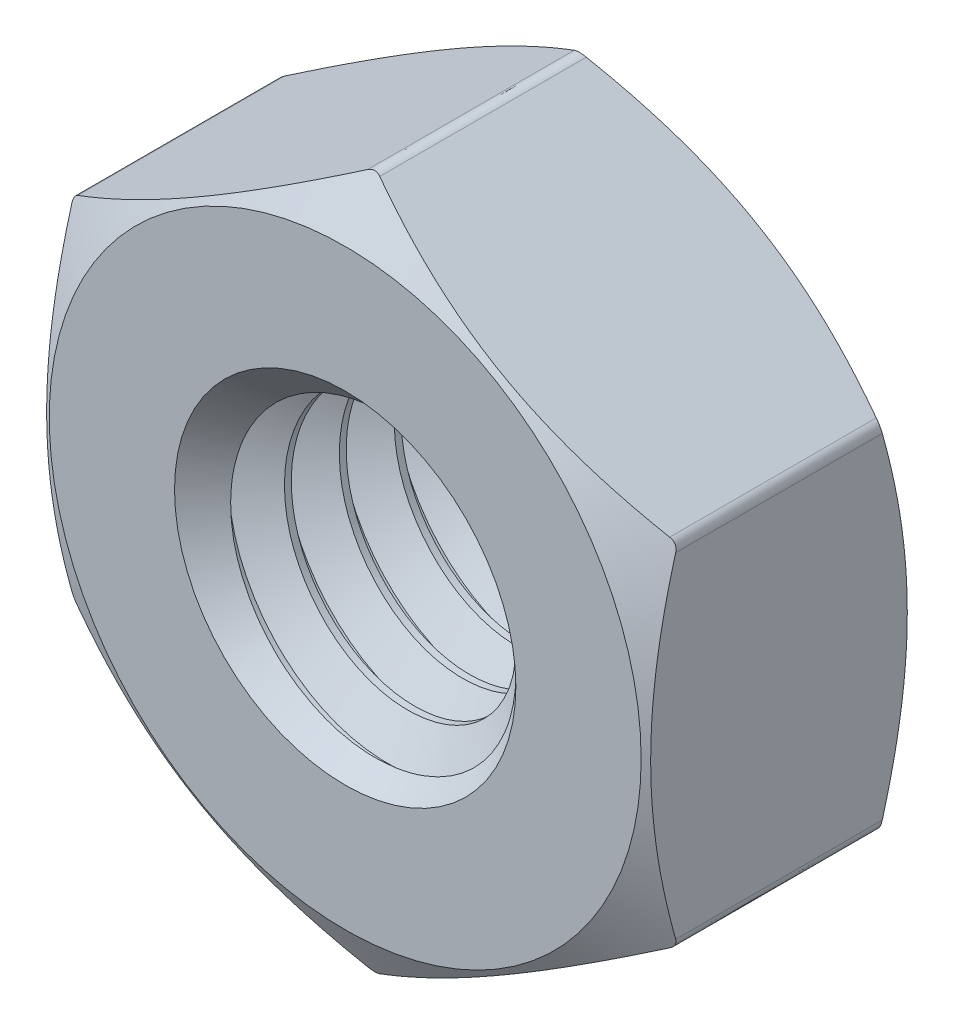
SolidWorks part; units mm, degrees
material "AISI 316 Annealed Stainless Steel Bar (SS)"
ref_plane "Front Plane" through (0, 0, 0) normal (0, 0, 1) x (1, 0, 0)
ref_plane "Top Plane" through (0, 0, 0) normal (0, 1, 0) x (1, 0, 0)
ref_plane "Right Plane" through (0, 0, 0) normal (1, 0, 0) x (0, 0, -1)
sketch "Sketch1" plane through (0, 0, 0) normal (0, 0, 1) x (1, 0, 0)
  line L0 (0, -3.1754) -> (0, 3.1754) construction
  line L1 (0, -3.1754) -> (2.75, -1.5877) construction
  line L2 (2.75, -1.5877) -> (2.75, 1.5877) construction
  line L3 (2.75, 1.5877) -> (0, 3.1754) construction
  line L4 (0, 3.1754) -> (-2.75, 1.5877) construction
  line L5 (-2.75, 1.5877) -> (-2.75, -1.5877) construction
  line L6 (-2.75, -1.5877) -> (0, -3.1754) construction
  line L7 (-2.75, 0) -> (2.75, 0) construction
  line L8 (0, 0) -> (0.75, -1.299) construction
  circle A0 centre (0, 0) radius 2.75 construction
  circle A1 centre (0, 0) radius 1.5 construction
  point P11 (0, 0)
  point P12 (0, -1.5)
  point P14 (1.5, 0)
  point P15 (0, 1.5)
  point P16 (-1.5, 0)
  point P19 (0.75, -1.299)
  dimension "Thread Diameter" = 3
  dimension "Width" = 5.5
  dimension "D1" = 30
sketch "Sketch2" plane through (0, 0, 0) normal (1, 0, 0) x (0, 0, -1)
  line L0 (0, -2.75) -> (0, 2.75) construction
  line L1 (-1.2, 2.75) -> (1.2, 2.75) construction
  line L2 (-1.2, 2.75) -> (-1.2, -2.75) construction
  line L3 (-1.2, -2.75) -> (1.2, -2.75) construction
  line L4 (1.2, 2.75) -> (1.2, -2.75) construction
  line L5 (1.2, 0) -> (-1.2, 0) construction
  line L8 (-1.2, 1.5) -> (1.2, 1.5) construction
  line L9 (-1.2, -1.5) -> (1.2, -1.5) construction
  line L10 (-1.6688, 1.5541) -> (-1.1687, 1.5541) construction
  line L11 (-1.1687, 1.5541) -> (-1.4187, 1.1211) construction
  line L12 (-1.4187, 1.1211) -> (-1.6688, 1.5541) construction
  line L13 (-1.6531, 1.5271) -> (-1.1844, 1.5271) construction
  line L14 (-1.6375, 1.5) -> (-1.2, 1.5) construction
  line L15 (-1.45, 1.1752) -> (-1.3875, 1.1752) construction
  line L16 (-1.4187, 1.1752) -> (-1.4187, 1.1211) construction
  line L17 (-1.4187, 1.5541) -> (-1.4187, 1.5) construction
  point P8 (0, 0)
  point P29 (-1.4187, 1.5271)
  dimension "Height" = 2.4
  dimension "Thread Pitch" = 0.5
  dimension "D2" = 0.0625
sketch "Sketch3" plane through (0, 0, 0) normal (0, 0, 1) x (1, 0, 0)
  line L1 (0, -3.1754) -> (2.75, -1.5877)
  line L2 (2.75, -1.5877) -> (2.75, 1.5877)
  line L3 (2.75, 1.5877) -> (0, 3.1754)
  line L4 (0, 3.1754) -> (-2.75, 1.5877)
  line L5 (-2.75, 1.5877) -> (-2.75, -1.5877)
  line L6 (-2.75, -1.5877) -> (0, -3.1754)
  circle A0 centre (0, 0) radius 2.75 construction
  circle A1 centre (0, 0) radius 1.1752
extrude "Boss-Extrude1" add sketch "Sketch3" along normal up to vertex (1.2 mm away) and the other way up to vertex (1.2 mm away) up to point (0, 0, 1.2) other way up to point (0, 0, -1.2)
sketch "Sketch4" plane through (0, 0, 0) normal (0, 0, 1) x (1, 0, 0)
  circle A0 centre (0, 0) radius 2.695
  dimension "D1" = 5.39
extrude "Cut-Extrude1" cut sketch "Sketch4" against normal through all draft 60 from vertex flip side to cut starting at point (0, 0, 1.2)
extrude "Cut-Extrude2" cut sketch "Sketch4<2>" along normal through all draft 60 from vertex flip side to cut starting at point (0, 0, -1.2)
sketch "Sketch4<2>" plane through (0, 0, 0) normal (0, 0, 1) x (1, 0, 0) same geometry as "Sketch4"
chamfer "Chamfer1" distance 0.3125 angle 45 2 edges at (1.1752, 0, -1.2) (1.1752, 0, 1.2)
fillet "Fillet1" radius 0.11 6 edges at (-2.75, -1.5877, 0) (-2.75, 1.5877, 0) (0, -3.1754, 0) (2.75, -1.5877, 0) (0, 3.1754, 0) (2.75, 1.5877, 0) conic rho 0.5
ref_axis "Center Axis 1" through (0, 0, -5.9323) along (0, 0, 1)
sketch "Sketch5" plane through (0, 0, 0) normal (0, 0, 1) x (1, 0, 0)
  circle A0 centre (0, 0) radius 1.5 construction
  circle A1 centre (0, 0) radius 1.5
extrude "Cut-Extrude3" cut sketch "Sketch5" against normal through all both and the other way through all
sketch "Sketch6" plane through (0, 0, 1.2) normal (0, 0, 1) x (1, 0, 0)
  circle A0 centre (0, 0) radius 1.5 construction
  circle A1 centre (0, 0) radius 1.5
curve "Helix/Spiral1" pitch 0.5 height 2.9 radius 1.5 centre (0, 0, 1.2) axis (0, 0, -1) start towards (0, 1, 0)
sketch "Sketch7" plane through (0, 0, 0) normal (1, 0, 0) x (0, 0, -1)
  line L0 (-1.6531, 1.5271) -> (-1.1844, 1.5271)
  line L1 (-1.1844, 1.5271) -> (-1.3875, 1.1752)
  line L2 (-1.3875, 1.1752) -> (-1.45, 1.1752)
  line L3 (-1.45, 1.1752) -> (-1.6531, 1.5271)
sweep "Sweep1" add profiles "Sketch7" path "Helix/Spiral1"
sketch "Sketch8" plane through (0, 0, 1.2) normal (0, 0, 1) x (1, 0, 0)
  circle A0 centre (0, 0) radius 1.5541
extrude "Cut-Extrude4" cut sketch "Sketch8" against normal through all draft 45 and the other way through all
sketch "Sketch9" plane through (0, 0, -1.2) normal (0, 0, -1) x (-1, 0, 0)
  circle A1 centre (0, 0) radius 1.5541
  circle A2 centre (0, 0) radius 1.5541
  dimension "D1" = 0
extrude "Cut-Extrude5" cut sketch "Sketch9" against normal through all draft 45 and the other way through all
equation "\"D2@Sketch2\" = \"Thread Pitch@Sketch2\" / 8"
equation "\"D1@Chamfer1\"=\"Thread Pitch@Sketch2\"*.625"
equation "\"D1@Sketch4\"=\"Width@Sketch1\"*.98"
equation "\"D1@Fillet1\"=\"Width@Sketch1\"*.02"
equation "\"D4@Helix/Spiral1\"=\"Thread Pitch@Sketch2\""
equation "\"D3@Helix/Spiral1\"=\"Height@Sketch2\"+\"Thread Pitch@Sketch2\""
equation "\"D3@Cut-Extrude2\"=\"D3@Cut-Extrude1\""
